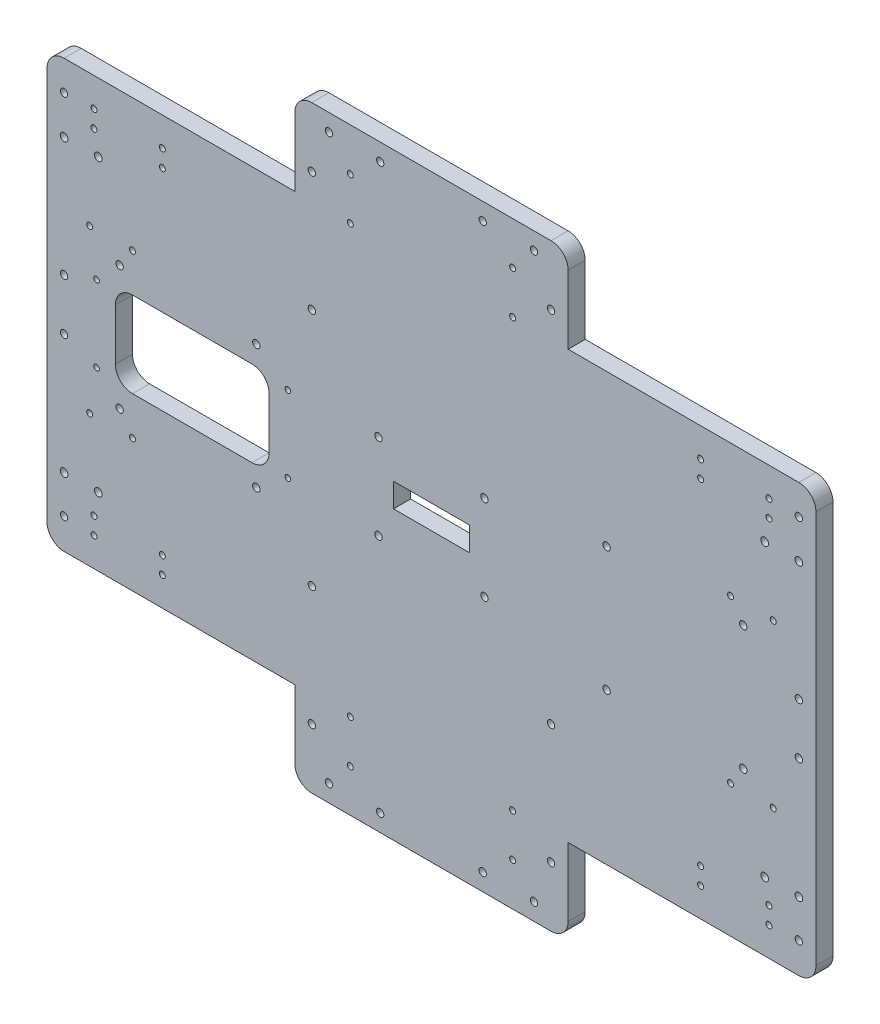
SolidWorks part; units mm, degrees
ref_plane "Front Plane" through (0, 0, 0) normal (0, 0, 1) x (1, 0, 0)
ref_plane "Top Plane" through (0, 0, 0) normal (0, 1, 0) x (1, 0, 0)
ref_plane "Right Plane" through (0, 0, 0) normal (1, 0, 0) x (0, 0, -1)
sketch "Model" plane through (0, 0, 0) normal (0, 0, 1) x (1, 0, 0)
  line L0 (247.1997, 167.9993) -> (247.1997, 182.0007)
  line L1 (202.8003, 167.9993) -> (247.1997, 167.9993)
  line L2 (202.8003, 182.0007) -> (202.8003, 167.9993)
  line L3 (247.1997, 182.0007) -> (202.8003, 182.0007)
  line L4 (0, 60) -> (0, 290)
  line L5 (145, 50) -> (10, 50)
  line L6 (145, 10) -> (145, 50)
  line L7 (155, 0) -> (295, 0)
  line L8 (305, 50) -> (305, 10)
  line L9 (440, 50) -> (305, 50)
  line L10 (450, 60) -> (450, 290)
  line L11 (305, 300) -> (440, 300)
  line L12 (305, 340) -> (305, 300)
  line L13 (155, 350) -> (295, 350)
  line L14 (145, 300) -> (145, 340)
  line L15 (10, 300) -> (145, 300)
  line L16 (120, 200) -> (50, 200)
  line L17 (130, 160) -> (130, 190)
  line L18 (50, 150) -> (120, 150)
  line L19 (40, 190) -> (40, 160)
  circle A0 centre (122.5, 138.6571) radius 2.15
  circle A1 centre (255, 10) radius 2.15
  circle A2 centre (285, 10) radius 2.15
  circle A3 centre (295, 35) radius 2.15
  circle A4 centre (295, 105) radius 2.15
  circle A5 centre (295, 315) radius 2.15
  circle A6 centre (285, 340) radius 2.15
  circle A7 centre (194, 150) radius 2.15
  circle A8 centre (256, 150) radius 2.15
  circle A9 centre (256, 200) radius 2.15
  circle A10 centre (194, 200) radius 2.15
  circle A11 centre (407.5, 211.3429) radius 2.15
  circle A12 centre (407.5, 138.6571) radius 2.15
  circle A13 centre (327.5, 138.6571) radius 2.15
  circle A14 centre (42.5, 138.6571) radius 2.15
  circle A15 centre (440, 160.1892) radius 2.15
  circle A16 centre (440, 190.1892) radius 2.15
  circle A17 centre (440, 282.5) radius 2.15
  circle A18 centre (155, 35) radius 2.15
  circle A19 centre (10, 67.8783) radius 2.15
  circle A20 centre (10, 190.1892) radius 2.15
  circle A21 centre (10, 160.1892) radius 2.15
  circle A22 centre (440, 67.8783) radius 2.15
  circle A23 centre (195, 340) radius 2.15
  circle A24 centre (165, 10) radius 2.15
  circle A25 centre (195, 10) radius 2.15
  circle A26 centre (255, 340) radius 2.15
  circle A27 centre (155, 105) radius 2.15
  circle A28 centre (155, 315) radius 2.15
  circle A29 centre (155, 245) radius 2.15
  circle A30 centre (165, 340) radius 2.15
  circle A31 centre (42.5, 211.3429) radius 2.15
  circle A32 centre (122.5, 211.3429) radius 2.15
  circle A33 centre (327.5, 211.3429) radius 2.15
  circle A34 centre (10, 282.5) radius 2.15
  circle A35 centre (141, 197.3) radius 1.65
  circle A36 centre (141, 152.7) radius 1.65
  circle A37 centre (29, 152.7) radius 1.65
  circle A38 centre (29, 197.3) radius 1.65
  arc A39 (0, 60) -> (10, 50) centre (10, 60) ccw
  arc A40 (145, 10) -> (155, 0) centre (155, 10) ccw
  arc A41 (295, 0) -> (305, 10) centre (295, 10) ccw
  arc A42 (440, 50) -> (450, 60) centre (440, 60) ccw
  arc A43 (450, 290) -> (440, 300) centre (440, 290) ccw
  arc A44 (305, 340) -> (295, 350) centre (295, 340) ccw
  arc A45 (155, 350) -> (145, 340) centre (155, 340) ccw
  arc A46 (10, 300) -> (0, 290) centre (10, 290) ccw
  circle A47 centre (67.5, 273.0996) radius 1.75
  circle A48 centre (27.5, 283.0996) radius 1.75
  circle A49 centre (27.5, 273.0996) radius 1.75
  circle A50 centre (382.5, 273.0996) radius 1.75
  circle A51 centre (27.5, 66.9004) radius 1.75
  circle A52 centre (67.5, 66.9004) radius 1.75
  circle A53 centre (67.5, 76.9004) radius 1.75
  circle A54 centre (67.5, 283.0996) radius 1.75
  circle A55 centre (422.5, 76.9004) radius 1.75
  circle A56 centre (382.5, 76.9004) radius 1.75
  circle A57 centre (382.5, 66.9004) radius 1.75
  circle A58 centre (422.5, 66.9004) radius 1.75
  circle A59 centre (422.5, 273.0996) radius 1.75
  circle A60 centre (422.5, 283.0996) radius 1.75
  circle A61 centre (382.5, 283.0996) radius 1.75
  circle A62 centre (27.5, 76.9004) radius 1.75
  circle A63 centre (25, 127.5) radius 1.75
  circle A64 centre (50, 127.5) radius 1.75
  circle A65 centre (177.5, 325.0262) radius 1.75
  circle A66 centre (50, 222.5) radius 1.75
  circle A67 centre (272.5, 24.9738) radius 1.75
  circle A68 centre (177.5, 49.9738) radius 1.75
  circle A69 centre (177.5, 24.9738) radius 1.75
  circle A70 centre (25, 222.5) radius 1.75
  circle A71 centre (425, 222.5) radius 1.75
  circle A72 centre (400, 222.5) radius 1.75
  circle A73 centre (400, 127.5) radius 1.75
  circle A74 centre (272.5, 325.0262) radius 1.75
  circle A75 centre (272.5, 300.0262) radius 1.75
  circle A76 centre (177.5, 300.0262) radius 1.75
  circle A77 centre (425, 127.5) radius 1.75
  circle A78 centre (272.5, 49.9738) radius 1.75
  circle A79 centre (10, 90) radius 2.25
  circle A80 centre (30, 90) radius 2.25
  circle A81 centre (420, 90) radius 2.25
  circle A82 centre (440, 90) radius 2.25
  circle A83 centre (440, 260) radius 2.25
  circle A84 centre (420, 260) radius 2.25
  circle A85 centre (30, 260) radius 2.25
  circle A86 centre (10, 260) radius 2.25
  arc A87 (50, 200) -> (40, 190) centre (50, 190) ccw
  arc A88 (130, 190) -> (120, 200) centre (120, 190) ccw
  arc A89 (120, 150) -> (130, 160) centre (120, 160) ccw
  arc A90 (40, 160) -> (50, 150) centre (50, 160) ccw
  text T0 "SOLIDWORKS Educational Product." font "SWTXT" height 4.8336
  text T1 "For Instructional Use Only." font "SWTXT" height 4.8336
extrude "Boss-Extrude2" add sketch "Model" along normal blind 10
sketch "Sketch2" plane through (0, 0, 10) normal (0, 0, 1) x (1, 0, 0)
  line L1 (-8.6811, 5.8884) -> (109.0847, 5.8884)
  line L2 (-8.6811, 5.8884) -> (-8.6811, -28.7683)
  line L3 (-8.6811, -28.7683) -> (109.0847, -28.7683)
  line L4 (109.0847, 5.8884) -> (109.0847, -28.7683)
extrude "Cut-Extrude1" cut sketch "Sketch2" against normal through all
